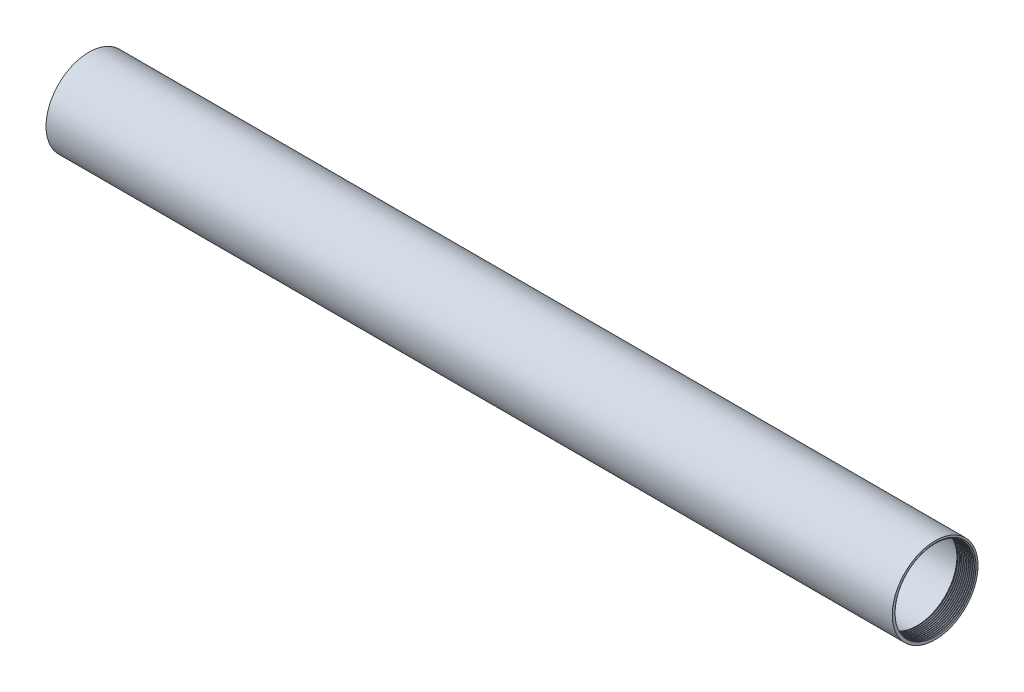
SolidWorks part; units mm, degrees
material "6061-T6 (SS)"
ref_plane "Front Plane" through (0, 0, 0) normal (0, 0, 1) x (1, 0, 0)
ref_plane "Top Plane" through (0, 0, 0) normal (0, 1, 0) x (1, 0, 0)
ref_plane "Right Plane" through (0, 0, 0) normal (1, 0, 0) x (0, 0, -1)
sketch "Sketch1" plane through (0, 0, 0) normal (0, 0, 1) x (1, 0, 0)
  line L0 (0, 37.719) -> (743.966, 37.719)
  line L1 (0, 0) -> (743.966, 0) construction
  line L2 (0, 37.719) -> (0, 35.2425)
  line L3 (0, 35.2425) -> (15.875, 35.2425)
  line L4 (15.875, 35.2425) -> (15.875, 34.925)
  line L5 (15.875, 34.925) -> (728.091, 34.925)
  line L6 (728.091, 34.925) -> (728.091, 35.2425)
  line L7 (728.091, 35.2425) -> (743.966, 35.2425)
  line L8 (743.966, 35.2425) -> (743.966, 37.719)
  point P6 (743.966, 36.4807)
  dimension "D1" = 743.966
  dimension "D2" = 34.925
  dimension "D3" = 37.719
  dimension "D4" = 35.2425
  dimension "D5" = 15.875
  dimension "D6" = 15.875
revolve "Revolve1" add sketch "Sketch1" angle 360 about L1
thread "Thread1" pitch 1.5875 method cut trim with start face yes trim with end face yes profile "Thread Profile1" start angle 0, offset 1.5875, length 0, pitch 1.5875, diameter 70.485
ref_plane "Plane1" through (17.4625, 0, 35.2425) normal (0, -1, 0) x (0, 0, 1)
sketch "Thread Profile1" plane through (17.4625, 0, 35.2425) normal (0, -1, 0) x (0, 0, 1)
  line L0 (0, 0) -> (0, 1.5875) construction
  line L1 (0, 0) -> (0.8593, 0.4961)
  line L2 (0.8593, 0.4961) -> (0.8593, 0.6945)
  line L3 (0.8593, 0.6945) -> (0, 1.1906)
  line L4 (0.8593, 0.5953) -> (0, 0.5953) construction
  line L11 (0, 0) -> (0, 1.1906)
  point P2 (0, 0)
  dimension "Pitch" = 1.5875
  dimension "Profile_Angle" = 60
  dimension "Profile_Land" = 0.1984
  dimension "Profile_Height" = 0.8593
thread "Thread2" pitch 1.5875 method cut trim with start face yes trim with end face yes profile "Thread Profile2" start angle 180, offset 1.5875, length 0, pitch 1.5875, diameter 70.485
ref_plane "Plane2" through (726.5035, 0, 35.2425) normal (0, 1, 0) x (0, 0, 1)
sketch "Thread Profile2" plane through (726.5035, 0, 35.2425) normal (0, 1, 0) x (0, 0, 1)
  line L0 (0, 0) -> (0, 1.5875) construction
  line L1 (0, 0) -> (0.8593, 0.4961)
  line L2 (0.8593, 0.4961) -> (0.8593, 0.6945)
  line L3 (0.8593, 0.6945) -> (0, 1.1906)
  line L4 (0.8593, 0.5953) -> (0, 0.5953) construction
  line L11 (0, 0) -> (0, 1.1906)
  point P2 (0, 0)
  dimension "Pitch" = 1.5875
  dimension "Profile_Angle" = 60
  dimension "Profile_Land" = 0.1984
  dimension "Profile_Height" = 0.8593
equation "\"D3@Sketch1\"=2.97/2"
equation "\"D6@Sketch1\"=\"D5@Sketch1\""
equation "\"D4@Sketch1\"=2.775/2"
equation "\"D2@Sketch1\"=2.75/2in"
